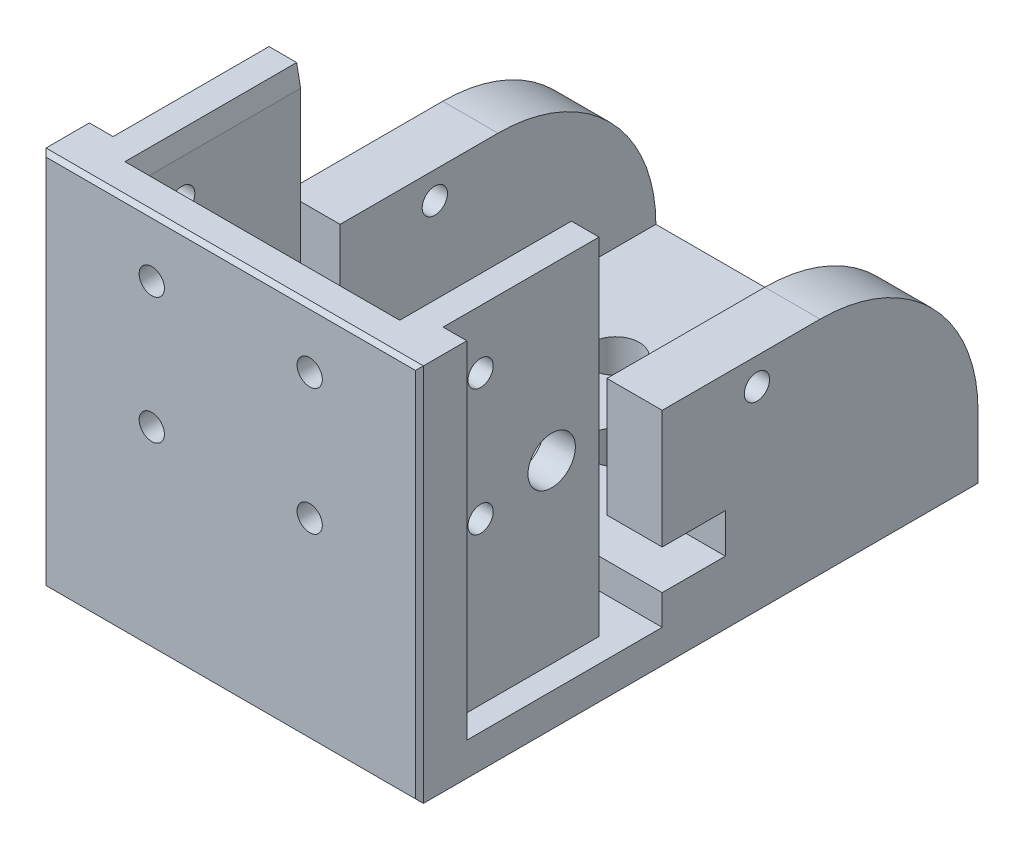
SolidWorks part; units mm, degrees
note: The reader was unsure of these and kept them because the rebuilt part matched: shared geometry of "草图1<3>".
other "标注1"
sketch "草图15" plane through (-23.9, -8, 13.875) normal (0, 0, 1) x (1, 0, 0)
ref_plane "Front" through (0, 0, 0) normal (0, 0, 1) x (1, 0, 0)
ref_plane "Top" through (0, 0, 0) normal (0, 1, 0) x (1, 0, 0)
ref_plane "Right" through (0, 0, 0) normal (1, 0, 0) x (0, 0, -1)
sketch "草图1" plane through (0, 0, 0) normal (0, 1, 0) x (1, 0, 0)
  line L0 (-16.9, 13.875) -> (-16.9, -9.875)
  line L1 (20.9, 13.875) -> (-20.9, 13.875)
  line L2 (20.9, 13.875) -> (20.9, -13.875)
  line L3 (20.9, -13.875) -> (-20.9, -13.875)
  line L4 (-20.9, 13.875) -> (-20.9, -13.875)
  line L5 (20.9, 13.875) -> (-20.9, -13.875) construction
  line L6 (20.9, -13.875) -> (-20.9, 13.875) construction
  line L7 (-16.9, -9.875) -> (16.9, -9.875)
  line L8 (16.9, -9.875) -> (16.9, 13.875)
  line L10 (20.9, 13.875) -> (-20.9, 13.875)
  line L11 (20.9, 13.875) -> (20.9, 56.875)
  line L12 (20.9, 56.875) -> (-20.9, 56.875)
  line L13 (-20.9, 13.875) -> (-20.9, 56.875)
  line L14 (-5, 29.875) -> (5, 29.875) construction
  line L15 (-5, 29.875) -> (-5, 39.875) construction
  line L16 (-5, 39.875) -> (5, 39.875) construction
  line L17 (5, 29.875) -> (5, 39.875) construction
  line L18 (-5, 29.875) -> (5, 39.875) construction
  line L19 (-5, 39.875) -> (5, 29.875) construction
  circle A0 centre (0, 34.875) radius 4.125 construction
  circle A6 centre (-5, 39.875) radius 1.6
  circle A7 centre (5, 39.875) radius 1.6
  circle A8 centre (5, 29.875) radius 1.6
  circle A9 centre (-5, 29.875) radius 1.6
  point P0 (0, 0)
  point P23 (0, 56.875)
  dimension "D7" = 8.25
  dimension "D11" = 10
  dimension "D19" = 33.8
  dimension "D10" = 3.2
  dimension "D2" = 27.75
  dimension "D3" = 4
  dimension "D4" = 4
  dimension "D5" = 4
  dimension "D6" = 43
  dimension "D8" = 0
  dimension "D9" = 22
  dimension "D12" = 10
extrude "凸台-拉伸1" add sketch "草图1" along normal blind 40 contours L8 L7 L0 L1 L4 L3 L2
extrude "凸台-拉伸2" add sketch "草图1<3>" against normal blind 8 contours L7 L8 L1 L0 | L8 L7 L0 L1 L4 L3 L2 | L13 L1 L11 L12
sketch "草图1<3>" plane through (0, 0, 0) normal (0, 1, 0) x (1, 0, 0) same geometry as "草图1"
sketch "草图4" plane through (20.9, 0, 0) normal (1, 0, 0) x (0, 0, -1)
  line L0 (-13.875, 40) -> (-13.875, -8) construction
  line L1 (56.875, -8) -> (-13.875, -8) construction
  circle A0 centre (-3.125, 16.6) radius 1.6
  circle A1 centre (-3.125, 32.6) radius 1.6
  dimension "D4" = 3.2
  dimension "D5" = 3.2
  dimension "D1" = 10.75
  dimension "D2" = 10.75
  dimension "D3" = 16
  dimension "D6" = 24.6
extrude "切除-拉伸1" cut sketch "草图4" against normal through all
sketch "草图8" plane through (0, 0, 0) normal (0, 1, 0) x (1, 0, 0)
  line L0 (20.9, 56.875) -> (-20.9, 56.875) construction
  line L1 (20.9, 13.875) -> (16.9, 13.875)
  line L2 (20.9, 13.875) -> (20.9, 56.875)
  line L3 (20.9, 56.875) -> (16.9, 56.875)
  line L4 (16.9, 13.875) -> (16.9, 56.875)
  line L5 (16.9, -9.875) -> (16.9, 13.875) construction
  line L6 (-20.9, 13.875) -> (-16.9, 13.875)
  line L7 (-20.9, 13.875) -> (-20.9, 56.875)
  line L8 (-20.9, 56.875) -> (-16.9, 56.875)
  line L9 (-16.9, 13.875) -> (-16.9, 56.875)
  line L10 (-16.9, 13.875) -> (-16.9, -9.875) construction
  dimension "D1" = 0
  dimension "D2" = 0
extrude "凸台-拉伸3" add sketch "草图8" along normal blind 20
sketch "草图11" plane through (20.9, 0, 0) normal (1, 0, 0) x (0, 0, -1)
  line L0 (-13.875, 40) -> (13.875, 40)
  line L1 (13.875, 40) -> (13.875, 20)
  line L2 (13.875, 20) -> (56.875, 20)
  line L3 (56.875, 20) -> (56.875, -8)
  line L4 (56.875, -8) -> (-13.875, -8)
  line L5 (-13.875, -8) -> (-13.875, 40)
  circle A0 centre (-3.125, 32.6) radius 1.6
  circle A1 centre (-3.125, 16.6) radius 1.6
  point P4 (-3.125, 32.6)
  point P13 (-3.125, 16.6)
  dimension "D1" = 3.2
  dimension "D2" = 3.2
extrude "凸台-拉伸5" add sketch "草图11" along normal blind 3
sketch "草图12" plane through (-20.9, 0, 0) normal (-1, 0, 0) x (0, 0, 1)
  line L0 (-13.875, 40) -> (13.875, 40)
  line L1 (13.875, 40) -> (13.875, -8)
  line L2 (13.875, -8) -> (-56.875, -8)
  line L3 (-56.875, -8) -> (-56.875, 20)
  line L4 (-56.875, 20) -> (-13.875, 20)
  line L5 (-13.875, 20) -> (-13.875, 40)
  circle A0 centre (3.125, 32.6) radius 1.6
  circle A1 centre (3.125, 16.6) radius 1.6
  point P12 (3.125, 32.6)
  point P16 (3.125, 16.6)
  dimension "D1" = 3.2
  dimension "D2" = 3.2
extrude "凸台-拉伸6" add sketch "草图12" along normal blind 3
fillet "圆角4" radius 20 2 edges at (20.4, 20, -56.875) (-20.4, 20, -56.875)
sketch "草图10" plane through (-23.9, 0, 0) normal (-1, 0, 0) x (0, 0, 1)
  circle A1 centre (-28.875, 16.6) radius 1.6
  circle A2 centre (3.125, 16.6) radius 1.6 construction
  point P0 (-28.875, 16.6)
  dimension "D3" = 3.2
  dimension "D2" = 32
  dimension "D1" = 0
extrude "切除-拉伸4" cut sketch "草图10" against normal through all
chamfer "倒角1" distance 0.5 angle 79 2 edges at (-16.9, 40, -2) (16.9, 40, -2)
sketch "草图5" plane through (0, 0, 13.875) normal (0, 0, 1) x (1, 0, 0)
  point P0 (-10, 16.6)
  point P1 (-10, 32.6)
  point P2 (10, 16.6)
  point P3 (10, 32.6)
hole_wizard "M3 间隙孔1" positions "草图6" profile "草图7" hole size "M3" standard "ISO" end condition up to next
sketch "草图6" plane through (0, 0, 13.875) normal (0, 0, 1) x (1, 0, 0)
  point P0 (-10, 32.6)
  point P3 (-10, 16.6)
  point P6 (10, 16.6)
  point P9 (10, 32.6)
sketch "草图7" plane through (-10, 32.6, 13.875) normal (1, 0, 0) x (0, -1, 0)
  line L0 (0, 0) -> (0, 4)
  line L1 (0, 4) -> (1.6, 4)
  line L2 (1.6, 4) -> (1.6, 0)
  line L5 (1.6, 0) -> (0, 0)
  line L11 (0, -6.35) -> (0, 107.95) construction
  dimension "通孔孔直径" = 3.2
  dimension "通孔孔深度" = 4
sketch "草图14" plane through (23.9, 0, 0) normal (1, 0, 0) x (0, 0, -1)
  line L0 (13.875, 20) -> (13.875, 40) construction
  line L1 (11.875, 44.6004) -> (16.875, 44.6004)
  line L2 (11.875, 44.6004) -> (11.875, -3.8098)
  line L3 (11.875, -3.8098) -> (16.875, -3.8098)
  line L4 (16.875, 44.6004) -> (16.875, -3.8098)
  dimension "D1" = 2
  dimension "D2" = 5
extrude "切除-拉伸6" cut sketch "草图14" against normal blind 10
sketch "草图22" plane through (0, 40, 0) normal (0, 1, 0) x (1, 0, 0)
  line L0 (23.9, 11.875) -> (23.9, -13.875) construction
  line L1 (26.7042, 14.9736) -> (20.9, 14.9736)
  line L2 (26.7042, 14.9736) -> (26.7042, -7.875)
  line L3 (26.7042, -7.875) -> (20.9, -7.875)
  line L4 (20.9, 14.9736) -> (20.9, -7.875)
  line L5 (23.9, -13.875) -> (-23.9, -13.875) construction
  dimension "D1" = 3
  dimension "D2" = 6
extrude "切除-拉伸11" cut sketch "草图22" against normal up to surface (43.8098 mm away) up to face at (18.9, -3.8098, -14.375)
mirror "镜向1" about plane through (0, 0, 0) normal (1, 0, 0) of "切除-拉伸11", "切除-拉伸6"
chamfer "倒角2" distance 0.5 angle 45 4 edges at (0, 40, 13.875) (0, -8, 13.875) (23.9, 16, 13.875) (-23.9, 16, 13.875)
sketch "草图13" plane through (23.9, 0, 0) normal (1, 0, 0) x (0, 0, -1)
  line L0 (-13.375, -8) -> (56.875, -8) construction
  line L1 (11.875, 5) -> (24.875, 5)
  line L2 (11.875, 5) -> (11.875, 0)
  line L3 (11.875, 0) -> (24.875, 0)
  line L4 (24.875, 5) -> (24.875, 0)
  line L5 (11.875, 40) -> (11.875, 0) construction
  circle A0 centre (-3.125, 16.6) radius 1.6 construction
  dimension "D2" = 28
  dimension "D3" = 8
  dimension "D4" = 5
extrude "切除-拉伸5" cut sketch "草图13" against normal blind 53
sketch "草图17" plane through (23.9, 0, 0) normal (1, 0, 0) x (0, 0, -1)
  line L0 (11.875, 40) -> (11.875, -3.8098) construction
  line L1 (-7.875, 40) -> (-13.375, 40) construction
  circle A0 centre (5.875, 18.5) radius 3
  dimension "D1" = 6
  dimension "D2" = 6
  dimension "D3" = 21.5
extrude "切除-拉伸8" cut sketch "草图17" against normal through all
sketch "草图19" plane through (0, -8, 0) normal (0, -1, 0) x (1, 0, 0)
  line L0 (-5, -29.875) -> (5, -39.875) construction
  line L1 (5, -39.875) -> (5, -29.875) construction
  line L2 (5, -29.875) -> (-5, -39.875) construction
  line L4 (-12.5, -47.375) -> (12.5, -47.375)
  line L5 (-12.5, -47.375) -> (-12.5, -22.375)
  line L6 (-12.5, -22.375) -> (12.5, -22.375)
  line L7 (12.5, -47.375) -> (12.5, -22.375)
  line L8 (-12.5, -47.375) -> (12.5, -22.375) construction
  line L9 (-12.5, -22.375) -> (12.5, -47.375) construction
  point P8 (0, -34.875)
  dimension "D1" = 25
extrude "凸台-拉伸7" add sketch "草图19" along normal blind 7
sketch "草图20" plane through (0, -15, 0) normal (0, -1, 0) x (1, 0, 0)
  line L0 (0, -22.375) -> (0, -48.7528) construction
  line L1 (-7.6, -42.475) -> (7.6, -42.475)
  line L2 (-7.6, -42.475) -> (-7.6, -27.275)
  line L3 (-7.6, -27.275) -> (7.6, -27.275)
  line L4 (7.6, -42.475) -> (7.6, -27.275)
  line L5 (-7.6, -42.475) -> (7.6, -27.275) construction
  line L6 (-7.6, -27.275) -> (7.6, -42.475) construction
  line L7 (12.5, -22.375) -> (-12.5, -22.375) construction
  line L8 (-12.5, -34.875) -> (10.5271, -34.875) construction
  line L9 (-12.5, -22.375) -> (-12.5, -47.375) construction
  point P0 (0, -34.875)
  dimension "D1" = 15.2
  dimension "D2" = 15.2
extrude "凸台-拉伸8" add sketch "草图20" along normal blind 2
chamfer "倒角3" distance 2 angle 45 4 edges at (7.6, -15, -34.875) (0, -15, -42.475) (-7.6, -15, -34.875) (0, -15, -27.275)
sketch "草图21" plane through (0, 0, 0) normal (0, 1, 0) x (1, 0, 0)
  circle A0 centre (-5, 39.875) radius 1.6
  circle A1 centre (5, 39.875) radius 1.6
  circle A2 centre (5, 29.875) radius 1.6
  circle A3 centre (-5, 29.875) radius 1.6
extrude "切除-拉伸10" cut sketch "草图21" against normal through all
sketch "草图18" plane through (0, 0, 0) normal (0, 1, 0) x (1, 0, 0)
  circle A0 centre (-5, 39.875) radius 3
  circle A1 centre (5, 39.875) radius 3
  circle A2 centre (5, 29.875) radius 3
  circle A3 centre (-5, 29.875) radius 3
  dimension "D1" = 6
extrude "切除-拉伸9" cut sketch "草图18" against normal blind 6
chamfer "倒角5" distance 7 angle 45 4 edges at (-12.5, -8, -34.875) (0, -8, -47.375) (12.5, -8, -34.875) (0, -8, -22.375)
